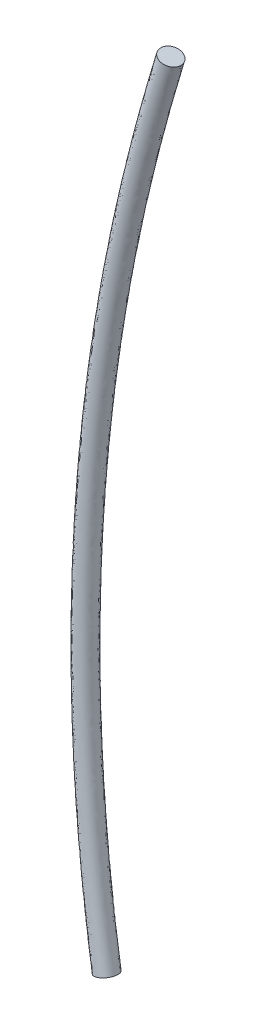
SolidWorks part; units mm, degrees
material "Custom Plastic"
ref_plane "X-Y Datum" through (0, 0, 0) normal (0, 0, 1) x (1, 0, 0)
ref_plane "X-Z Datum" through (0, 0, 0) normal (0, 1, 0) x (1, 0, 0)
ref_plane "Y-Z Datum" through (0, 0, 0) normal (1, 0, 0) x (0, 0, -1)
sketch3d "3DSketch2"
  circle A0 centre (-192.8639, 81.6813, 219.825) radius 4.5 construction
  spline S0 degree 2 poles (-192.8639, 81.6813, 219.825) (-228.1818, -42.4402, 223.9889) (-198.6168, -158.9053, 233.86) knots 0 0 0 0.949414 0.949414 0.949414
  point P8 (-194.403, 77.4526, 219.825)
  point P17 (-198.6168, -158.9053, 233.86)
sweep "Sweep2" add path "3DSketch2" circular profile diameter 6.35 parameters "D3"=6.35
